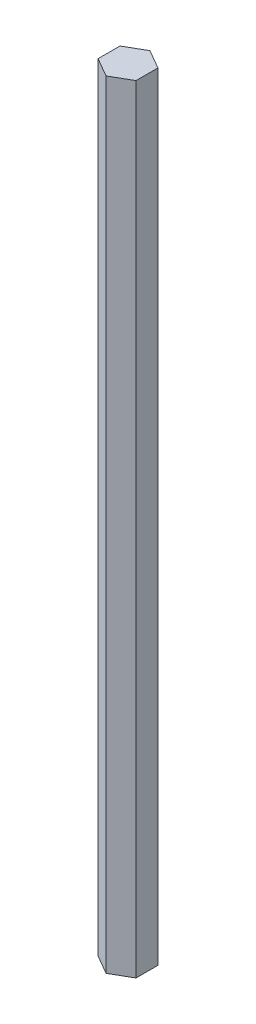
SolidWorks part; units mm, degrees
material "1023 Carbon Steel Sheet (SS)"
ref_plane "Front Plane" through (0, 0, 0) normal (0, 0, 1) x (1, 0, 0)
ref_plane "Top Plane" through (0, 0, 0) normal (0, 1, 0) x (1, 0, 0)
ref_plane "Right Plane" through (0, 0, 0) normal (1, 0, 0) x (0, 0, -1)
sketch "Sketch1" plane through (0, 0, 0) normal (0, 1, 0) x (1, 0, 0)
  line L1 (6.3495, -3.6671) -> (6.3505, 3.6653)
  line L2 (6.3505, 3.6653) -> (0.0011, 7.3323)
  line L3 (0.0011, 7.3323) -> (-6.3495, 3.6671)
  line L4 (-6.3495, 3.6671) -> (-6.3505, -3.6653)
  line L5 (-6.3505, -3.6653) -> (-0.0011, -7.3323)
  line L6 (-0.0011, -7.3323) -> (6.3495, -3.6671)
  circle A1 centre (0, 0) radius 6.35 construction
extrude "Boss-Extrude1" add sketch "Sketch1" along normal mid plane 260
ref_axis "Axis1" through (0, 176.9166, 0) along (0, -1, 0)
